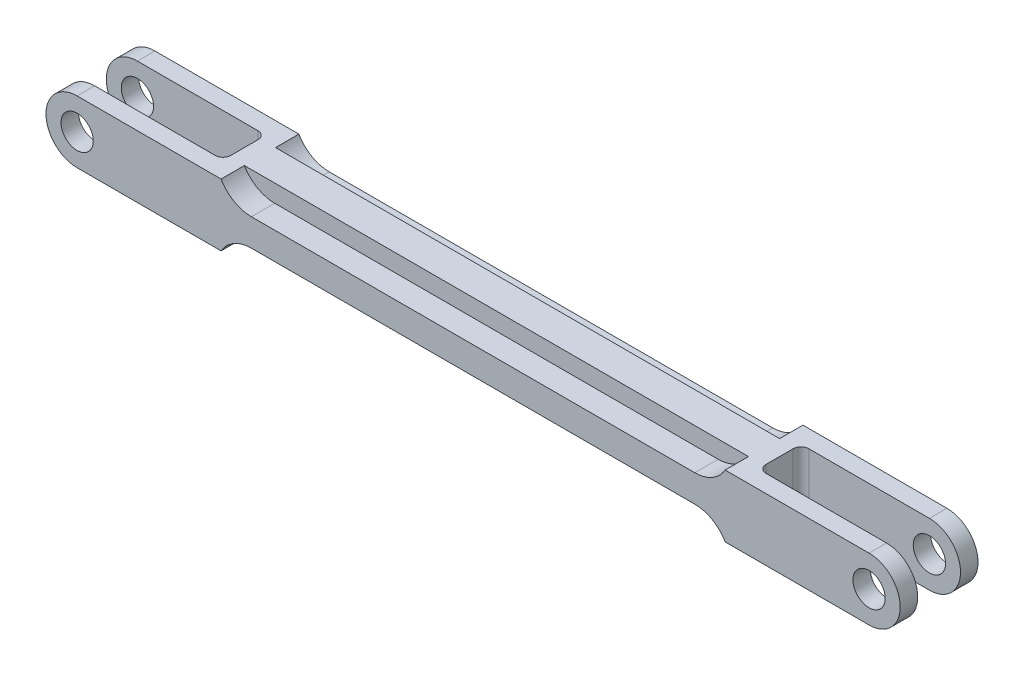
SolidWorks part; units mm, degrees
ref_plane "Front Plane" through (0, 0, 0) normal (0, 0, 1) x (1, 0, 0)
ref_plane "Top Plane" through (0, 0, 0) normal (0, 1, 0) x (1, 0, 0)
ref_plane "Right Plane" through (0, 0, 0) normal (1, 0, 0) x (0, 0, -1)
sketch "Sketch1" plane through (0, 0, 0) normal (0, 0, 1) x (1, 0, 0)
  line L0 (0, 0) -> (203.56, 0) construction
  line L1 (0, 8) -> (203.56, 8)
  line L2 (0, -8) -> (203.56, -8)
  line L3 (101.78, -24) -> (101.78, 8) construction
  arc A0 (0, 8) -> (0, -8) centre (0, 0) ccw
  arc A1 (203.56, -8) -> (203.56, 8) centre (203.56, 0) ccw
  circle A2 centre (0, 0) radius 4.15
  circle A3 centre (203.56, 0) radius 4.15
  point P3 (101.78, 0)
  point P11 (101.78, -8)
  dimension "D2" = 8
  dimension "D3" = 8.3
  dimension "D1" = 203.56
extrude "Corpo" add sketch "Sketch1" along normal mid plane 20
sketch "Sketch2" plane through (0, 8, 0) normal (0, 1, 0) x (1, 0, 0)
  line L0 (101.78, -10) -> (101.78, 10) construction
  line L1 (203.56, -10) -> (0, -10) construction
  line L2 (203.56, 10) -> (0, 10) construction
  line L3 (-8, 0) -> (211.56, 0) construction
  line L4 (-8, 10) -> (-8, -10) construction
  line L5 (211.56, -10) -> (211.56, 10) construction
  line L6 (170.56, 5.5) -> (211.56, 5.5)
  line L7 (33, -5.5) -> (-8, -5.5)
  line L8 (33, -5.5) -> (33, 5.5)
  line L9 (33, 5.5) -> (-8, 5.5)
  line L10 (-8, -5.5) -> (-8, 5.5)
  line L11 (33, -5.5) -> (-8, 5.5) construction
  line L12 (33, 5.5) -> (-8, -5.5) construction
  line L13 (211.56, -5.5) -> (211.56, 5.5)
  line L14 (170.56, -5.5) -> (211.56, -5.5)
  line L15 (170.56, -5.5) -> (170.56, 5.5)
  point P12 (12.5, 0)
  point P17 (101.78, 0)
  dimension "D1" = 41
  dimension "D2" = 11
extrude "Encaixe do Pino e Suporte" cut sketch "Sketch2" against normal through all
sketch "Sketch3" plane through (0, 8, 0) normal (0, 1, 0) x (1, 0, 0)
  line L0 (33, 0) -> (170.56, 0) construction
  line L1 (33, -5.5) -> (33, 5.5) construction
  line L2 (170.56, 5.5) -> (170.56, -5.5) construction
  line L3 (203.56, 10) -> (0, 10) construction
  line L4 (37, 10) -> (166.56, 10)
  line L5 (37, 10) -> (37, 4)
  line L6 (37, 4) -> (166.56, 4)
  line L7 (166.56, 10) -> (166.56, 4)
  line L8 (101.78, 0) -> (101.78, 10) construction
  line L9 (37, -4) -> (166.56, -4)
  line L10 (166.56, -10) -> (166.56, -4)
  line L11 (37, -10) -> (166.56, -10)
  line L12 (37, -10) -> (37, -4)
  point P14 (101.78, 10)
  dimension "D1" = 4
  dimension "D2" = 6
extrude "Corte Superior" cut sketch "Sketch3" against normal blind 4.5
mirror "Corte Inferior" about plane through (0, 0, 0) normal (0, 1, 0) of "Corte Superior"
fillet "Raios 9mm" radius 9 7 edges at (166.56, -3.5, 7) (166.56, -3.5, -7) (166.56, 3.5, 7) (166.56, 3.5, -7) (37, 3.5, -7) (37, 3.5, 7) (37, -3.5, 7)
fillet "Raios 2mm" radius 2 4 edges at (170.56, 0, -5.5) (170.56, 0, 5.5) (33, 0, -5.5) (33, 0, 5.5)
